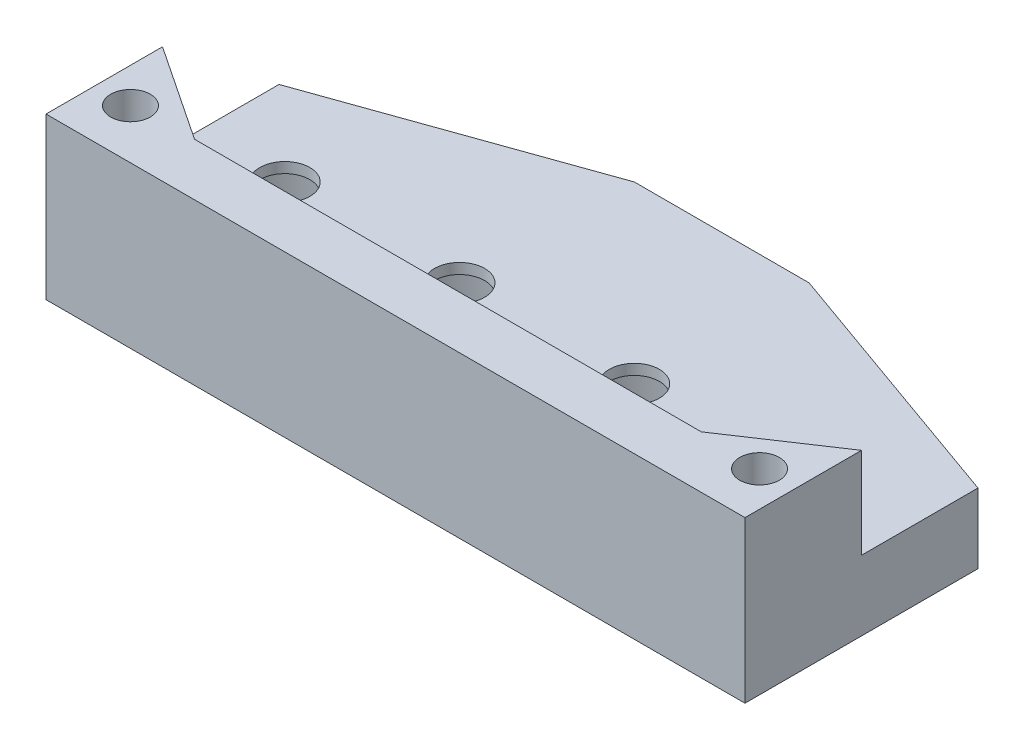
SolidWorks part; units mm, degrees
ref_plane "Front Plane" through (0, 0, 0) normal (0, 0, 1) x (1, 0, 0)
ref_plane "Top Plane" through (0, 0, 0) normal (0, 1, 0) x (1, 0, 0)
ref_plane "Right Plane" through (0, 0, 0) normal (1, 0, 0) x (0, 0, -1)
sketch "Sketch2" plane through (0, 0, 0) normal (0, 1, 0) x (1, 0, 0)
  line L0 (0, 0) -> (0, 20)
  line L1 (0, 20) -> (22.5, 28)
  line L2 (22.5, 28) -> (37.5, 28)
  line L3 (37.5, 28) -> (60, 20)
  line L4 (60, 20) -> (60, 0)
  line L5 (60, 0) -> (0, 0)
  line L6 (22.5, 13) -> (37.5, 13) construction
  line L7 (30, 28) -> (30, 0) construction
  circle A0 centre (7.5, 13) radius 2.15
  circle A1 centre (22.5, 13) radius 2.15
  circle A2 centre (37.5, 13) radius 2.15
  circle A3 centre (52.5, 13) radius 2.15
  point P17 (30, 13)
  dimension "D5" = 4.3
  dimension "D7" = 15
  dimension "D8" = 15
  dimension "D9" = 15
  dimension "D1" = 60
  dimension "D2" = 20
  dimension "D3" = 15
  dimension "D4" = 8
  dimension "D6" = 13
extrude "Boss-Extrude1" add sketch "Sketch2" along normal blind 6
sketch "Sketch3" plane through (0, 6, 0) normal (0, 1, 0) x (1, 0, 0)
  line L0 (0, 0) -> (0, 10)
  line L1 (0, 20) -> (0, 0) construction
  line L2 (0, 10) -> (15, 0)
  line L3 (0, 0) -> (60, 0) construction
  line L4 (15, 0) -> (0, 0)
  line L5 (60, 0) -> (60, 10)
  line L6 (60, 0) -> (60, 20) construction
  line L7 (60, 10) -> (45, 0)
  line L8 (45, 0) -> (60, 0)
  line L9 (51.75, 4.5) -> (8.25, 4.5)
  line M8 (0, 0) -> (60, 0)
  line M9 (60, 0) -> (60, 20)
  line M13 (0, 20) -> (0, 0)
  dimension "D1" = 15
  dimension "D2" = 10
  dimension "D3" = 4.5
extrude "Boss-Extrude2" add sketch "Sketch3" along normal blind 7.8 contours L2 M13 M8 | L7 L9 L2 M8 | L7 M9 M8 region at (5, 6, -3.3333) region at (30, 6, -2.3878) region at (55, 6, -3.3333)
sketch "Sketch4" plane through (0, 13.8, 0) normal (0, 1, 0) x (1, 0, 0)
  line L0 (0, 0) -> (60, 0) construction
  line L1 (0, 10) -> (0, 0) construction
  line L2 (60, 0) -> (60, 10) construction
  circle A0 centre (3, 4.25) radius 1.7
  circle A1 centre (57, 4.25) radius 1.7
  dimension "D1" = 3.4
  dimension "D2" = 4.25
  dimension "D3" = 3
  dimension "D4" = 3
extrude "Cut-Extrude1" cut sketch "Sketch4" against normal through all
sketch "Sketch5" plane through (0, 0, 0) normal (0, 1, 0) x (1, 0, 0)
  circle A0 centre (7.5, 13) radius 6.55
  circle A1 centre (22.5, 13) radius 6.55
  circle A2 centre (37.5, 13) radius 6.55
  circle A3 centre (52.5, 13) radius 6.55
  dimension "D1" = 13.1
extrude "Cut-Extrude2" cut sketch "Sketch5" along normal blind 5.1
